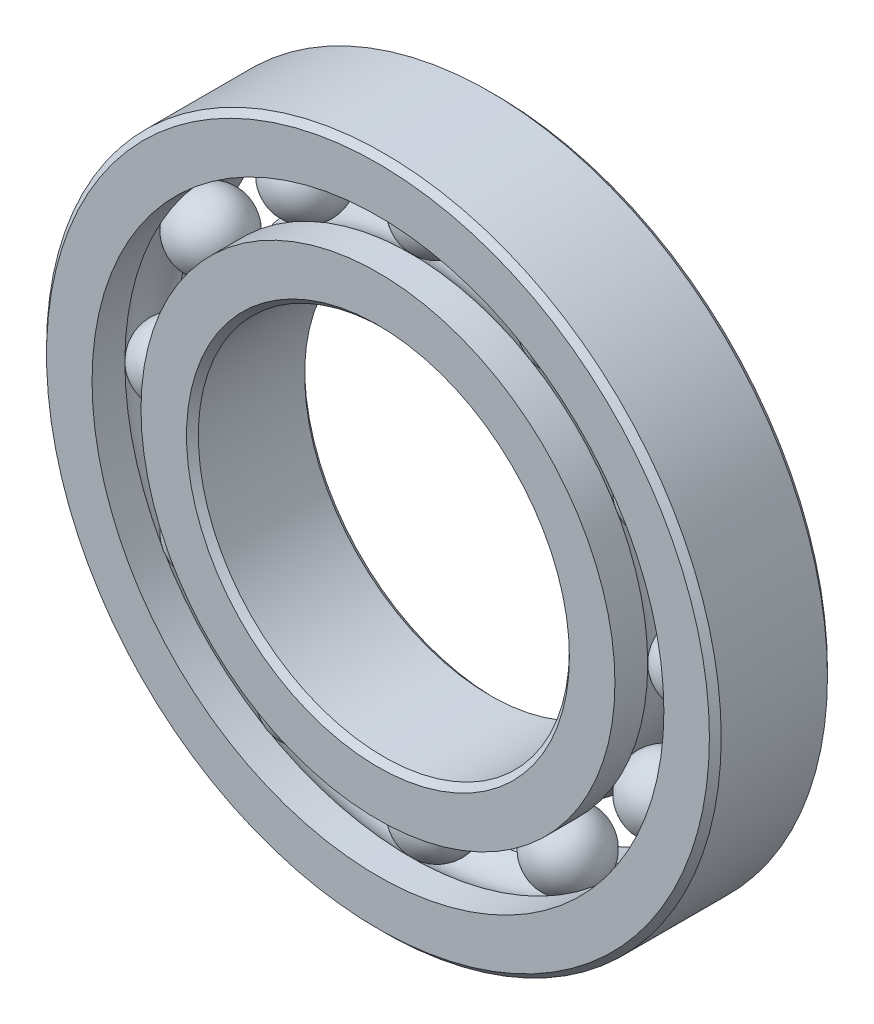
SolidWorks part; units mm, degrees
ref_plane "Front Plane" through (0, 0, 0) normal (0, 0, 1) x (1, 0, 0)
ref_plane "Top Plane" through (0, 0, 0) normal (0, 1, 0) x (1, 0, 0)
ref_plane "Right Plane" through (0, 0, 0) normal (1, 0, 0) x (0, 0, -1)
sketch "Sketch1" plane through (0, 0, 0) normal (1, 0, 0) x (0, 0, -1)
  line L0 (-5.5562, 0) -> (5.5562, 0) construction
  line L1 (0, 31.75) -> (0, -31.75) construction
  line L2 (5.0006, 31.75) -> (-5.0006, 31.75)
  line L3 (-5.0006, 31.75) -> (-5.5563, 31.1944)
  line L4 (-5.5563, 31.1944) -> (-5.5563, 26.909)
  line L5 (-5.5563, 26.909) -> (-2.4694, 26.909)
  line L6 (5.5563, 26.909) -> (2.4694, 26.909)
  line L7 (5.5563, 31.1944) -> (5.5563, 26.909)
  line L8 (5.0006, 31.75) -> (5.5563, 31.1944)
  line L9 (0, 31.75) -> (0, 24.6062) construction
  line L10 (0, 24.6062) -> (0, 17.4625) construction
  arc A0 (-2.4694, 26.909) -> (2.4694, 26.909) centre (0, 24.6062) cw
  point P14 (0, 17.4625)
  dimension "Width" = 11.1125
  dimension "OD" = 63.5
  dimension "D1" = 45
  dimension "D2" = 0.5556
  dimension "Shaft Dia" = 34.925
  dimension "D3" = 4.9389
  dimension "D4" = 2.3027
revolve "Revolve1" add sketch "Sketch1" angle 360 about L0
sketch "Sketch3" plane through (0, 0, 0) normal (1, 0, 0) x (0, 0, -1)
  line L0 (-5.5563, 22.3035) -> (-2.4694, 22.3035)
  line L1 (0, 31.75) -> (0, -31.75) construction
  line L2 (-5.5563, 31.1944) -> (-5.5563, 26.909) construction
  line L3 (-5.5563, 22.3035) -> (-5.5563, 18.0181)
  line L4 (-5.0006, 31.75) -> (-5.5563, 31.1944) construction
  line L5 (-5.5563, 18.0181) -> (-5.0006, 17.4625)
  line L6 (-5.0006, 17.4625) -> (5.0006, 17.4625)
  line L7 (5.0006, 31.75) -> (5.0006, -31.75) construction
  line L8 (5.0006, 17.4625) -> (5.5563, 18.0181)
  line L9 (5.5563, -31.1944) -> (5.5563, 31.1944) construction
  line L10 (5.5563, 18.0181) -> (5.5563, 22.3035)
  line L11 (5.5563, 22.3035) -> (2.4694, 22.3035)
  line L13 (5.0006, 31.75) -> (5.5563, 31.1944) construction
  arc A0 (2.4694, 26.909) -> (-2.4694, 26.909) centre (0, 24.6062) ccw construction
  arc A1 (2.4694, 22.3035) -> (-2.4694, 22.3035) centre (0, 24.6063) cw
revolve "Revolve3" add sketch "Sketch3" angle 360 about L0
sketch "Sketch4" plane through (0, 0, 0) normal (1, 0, 0) x (0, 0, -1)
  line L0 (-3.3765, 24.6062) -> (3.3765, 24.6062)
  arc A2 (-3.3765, 24.6062) -> (3.3765, 24.6062) centre (0, 24.6062) cw
  arc A3 (2.4694, 26.909) -> (-2.4694, 26.909) centre (0, 24.6062) ccw construction
revolve "Revolve4" add sketch "Sketch4" angle 360 about L0
ref_axis "Axis1" through (0, 0, -5.5562) along (0, 0, 1)
pattern_circular "CirPattern1" count 12 every 30 about axis through (0, 0, -5.5562) along (0, 0, 1) of bodies 104
sketch "Sketch5" plane through (0, 0, 0) normal (1, 0, 0) x (0, 0, -1)
  line L0 (-5.5563, 26.909) -> (-2.4694, 26.909) construction
  line L1 (-5.2784, 26.909) -> (-3.3765, 26.909)
  line L2 (-5.2784, 26.909) -> (-5.2784, 22.3035)
  line L3 (-5.2784, 22.3035) -> (-3.3765, 22.3035)
  line L4 (-3.3765, 26.909) -> (-3.3765, 22.3035)
  line L5 (-5.5563, 22.3035) -> (-2.4694, 22.3035) construction
  line L6 (5.5563, 26.909) -> (2.4694, 26.909) construction
  line L7 (5.2784, 26.909) -> (3.3765, 26.909)
  line L8 (5.2784, 26.909) -> (5.2784, 22.3035)
  line L9 (5.2784, 22.3035) -> (3.3765, 22.3035)
  line L10 (3.3765, 26.909) -> (3.3765, 22.3035)
  line L11 (5.5563, 22.3035) -> (2.4694, 22.3035) construction
  line L12 (-5.0006, 31.75) -> (-5.5563, 31.1944) construction
  point P18 (-5.2784, 31.4722)
revolve "Revolve5" [suppressed] add sketch "Sketch5" angle 360 about L0
equation "\"D2@Sketch1\" = \"Width@Sketch1\"*.05"
equation "\"D3@Sketch1\" = \"Width@Sketch1\"/2.25"
equation "\"D4@Sketch1\" = (((\"OD@Sketch1\"-\"Width@Sketch1\")/2)/3.25)/3.5"
equation "\"D2@CirPattern1\" = 360/\"Balls@CirPattern1\""
